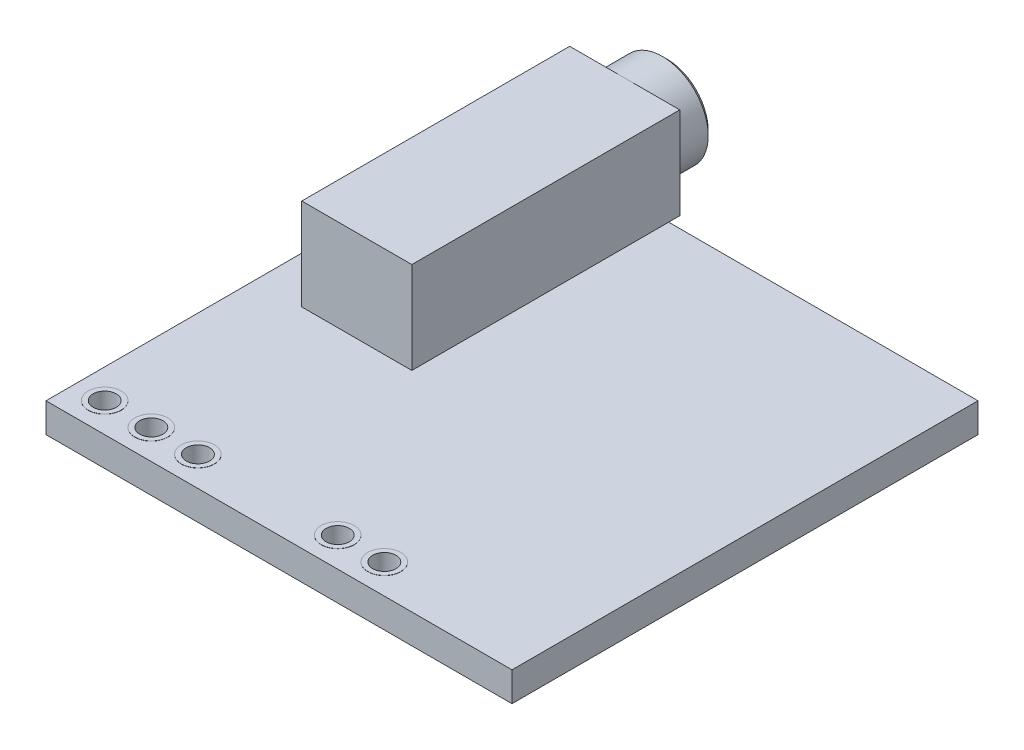
SolidWorks part; units mm, degrees
ref_plane "Front Plane" through (0, 0, 0) normal (0, 0, 1) x (1, 0, 0)
ref_plane "Top Plane" through (0, 0, 0) normal (0, 1, 0) x (1, 0, 0)
ref_plane "Right Plane" through (0, 0, 0) normal (1, 0, 0) x (0, 0, -1)
sketch "Sketch1" plane through (0, 0, 0) normal (0, 1, 0) x (1, 0, 0)
  line L0 (0, 0) -> (0, 12.7) construction
  line L1 (-12.7, 12.7) -> (12.7, 12.7)
  line L2 (-12.7, 12.7) -> (-12.7, -12.7)
  line L3 (-12.7, -12.7) -> (12.7, -12.7)
  line L4 (12.7, 12.7) -> (12.7, -12.7)
  line L5 (0, 0) -> (12.7, 0) construction
  dimension "D1" = 25.4
extrude "Boss-Extrude1" add sketch "Sketch1" along normal mid plane 1.6002
sketch "Sketch2" plane through (0, 0.8001, 0) normal (0, 1, 0) x (1, 0, 0)
  line L4 (-12.7, 12.7) -> (-12.7, -12.7)
  line L5 (-12.7, -12.7) -> (12.7, -12.7)
  line L6 (12.7, -12.7) -> (12.7, 12.7)
  line L7 (12.7, 12.7) -> (-12.7, 12.7)
  line L8 (-12.7, 12.7) -> (-12.7, -12.7)
  line L9 (-12.7, -12.7) -> (12.7, -12.7)
  line L10 (12.7, -12.7) -> (12.7, 12.7)
  line L11 (12.7, 12.7) -> (-12.7, 12.7)
  circle A0 centre (-11.0998, -11.0998) radius 0.635
  circle A1 centre (-8.5598, -11.0998) radius 0.635
  circle A2 centre (-6.0198, -11.0998) radius 0.635
  circle A3 centre (1.6002, -11.0998) radius 0.635
  circle A4 centre (4.1402, -11.0998) radius 0.635
  dimension "D8" = 1.27
  dimension "D2" = 1.6002
  dimension "D3" = 2.54
  dimension "D4" = 2.54
  dimension "D5" = 23.7998
  dimension "D6" = 7.62
  dimension "D7" = 2.54
  dimension "D1" = 0
extrude "Cut-Extrude1" cut sketch "Sketch2" against normal blind 1.6002 contours A0 | A1 | A2 | A3 | A4 region at (-11.0998, 0.8001, 11.0998) region at (-8.5598, 0.8001, 11.0998) region at (-6.0198, 0.8001, 11.0998) region at (1.6002, 0.8001, 11.0998) region at (4.1402, 0.8001, 11.0998)
sketch "Sketch3" plane through (0, 0.8001, 0) normal (0, 1, 0) x (1, 0, 0)
  line L0 (-7.16, 12.7) -> (-7.16, -1.3) construction
  line L2 (-10.16, 13.305) -> (-4.16, 13.305)
  line L3 (-10.16, 13.305) -> (-10.16, -1.3)
  line L4 (-12.7, 12.7) -> (-12.7, -12.7)
  line L5 (-12.7, -12.7) -> (12.7, -12.7)
  line L6 (12.7, -12.7) -> (12.7, 12.7)
  line L7 (12.7, 12.7) -> (-12.7, 12.7)
  line L8 (-12.7, 12.7) -> (-12.7, -12.7)
  line L9 (-12.7, -12.7) -> (12.7, -12.7)
  line L10 (12.7, -12.7) -> (12.7, 12.7)
  line L11 (12.7, 12.7) -> (-12.7, 12.7)
  line L12 (-10.16, -1.3) -> (-4.16, -1.3)
  line L13 (-4.16, 13.305) -> (-4.16, -1.3)
  line M13 (12.7, 12.7) -> (-12.7, 12.7)
  dimension "D2" = 6
  dimension "D3" = 2.54
  dimension "D4" = 14.605
  dimension "D5" = 14
  dimension "D1" = 0
extrude "Boss-Extrude2" add sketch "Sketch3" along normal blind 5 contours L0 L3 L12 M13 | L11 L0 L12 L13 | L13 L2 L3 L11 M13 region at (-5.66, 0.8001, -5.7) region at (-7.16, 0.8001, -13.0025) region at (-8.66, 0.8001, -5.7)
sketch "Sketch4" plane through (0, 0, -13.305) normal (0, 0, -1) x (-1, 0, 0)
  line L0 (7.16, 5.8001) -> (7.16, 0.8001) construction
  line L1 (4.16, 3.3001) -> (10.16, 3.3001) construction
  line L4 (4.16, 0.8001) -> (10.16, 0.8001)
  line L5 (10.16, 0.8001) -> (10.16, 5.8001)
  line L6 (10.16, 5.8001) -> (4.16, 5.8001)
  line L7 (4.16, 5.8001) -> (4.16, 0.8001)
  line L8 (4.16, 0.8001) -> (10.16, 0.8001)
  line L9 (10.16, 0.8001) -> (10.16, 5.8001)
  line L10 (10.16, 5.8001) -> (4.16, 5.8001)
  line L11 (4.16, 5.8001) -> (4.16, 0.8001)
  circle A0 centre (7.16, 3.3001) radius 2.5
  dimension "D2" = 5
  dimension "D1" = 0
extrude "Boss-Extrude3" add sketch "Sketch4" along normal blind 2.3 contours A0 region at (-7.16, 3.3001, -13.305)
sketch "Sketch5" plane through (0, 0, -15.605) normal (0, 0, -1) x (-1, 0, 0)
  circle A0 centre (7.16, 3.3001) radius 1.75
  circle A1 centre (7.16, 3.3001) radius 2.5
  circle A2 centre (7.16, 3.3001) radius 2.5
  dimension "D2" = 3.5
  dimension "D1" = 0
extrude "Cut-Extrude4" cut sketch "Sketch5" against normal offset from surface (15.905 mm away) 1 contours A0 region at (-7.16, 3.3001, -15.605) up to face at (-7.16, 3.3001, 1.3)
chamfer "Chamfer1" distance 0.25 angle 45 1 edges at (-9.66, 3.3001, -15.605)
sketch "Sketch6" plane through (0, 0.8001, 0) normal (0, 1, 0) x (1, 0, 0)
  line L8 (-10.16, -1.3) -> (-10.16, 12.7)
  line L9 (-10.16, 12.7) -> (-12.7, 12.7)
  line L10 (-12.7, 12.7) -> (-12.7, -12.7)
  line L11 (-12.7, -12.7) -> (12.7, -12.7)
  line L12 (12.7, -12.7) -> (12.7, 12.7)
  line L13 (12.7, 12.7) -> (-4.16, 12.7)
  line L14 (-4.16, 12.7) -> (-4.16, -1.3)
  line L15 (-4.16, -1.3) -> (-10.16, -1.3)
  line L16 (-10.16, -1.3) -> (-10.16, 12.7)
  line L17 (-10.16, 12.7) -> (-12.7, 12.7)
  line L18 (-12.7, 12.7) -> (-12.7, -12.7)
  line L19 (-12.7, -12.7) -> (12.7, -12.7)
  line L20 (12.7, -12.7) -> (12.7, 12.7)
  line L21 (12.7, 12.7) -> (-4.16, 12.7)
  line L22 (-4.16, 12.7) -> (-4.16, -1.3)
  line L23 (-4.16, -1.3) -> (-10.16, -1.3)
  circle A0 centre (-11.0998, -11.0998) radius 0.635 construction
  circle A1 centre (-8.5598, -11.0998) radius 0.635 construction
  circle A2 centre (-6.0198, -11.0998) radius 0.635 construction
  circle A3 centre (1.6002, -11.0998) radius 0.635 construction
  circle A4 centre (4.1402, -11.0998) radius 0.635 construction
  circle A5 centre (-11.0998, -11.0998) radius 0.635
  circle A6 centre (-8.5598, -11.0998) radius 0.635
  circle A7 centre (-6.0198, -11.0998) radius 0.635
  circle A8 centre (1.6002, -11.0998) radius 0.635
  circle A9 centre (4.1402, -11.0998) radius 0.635
  circle A10 centre (-11.0998, -11.0998) radius 0.9
  circle A11 centre (-8.5598, -11.0998) radius 0.9
  circle A12 centre (-6.0198, -11.0998) radius 0.9
  circle A13 centre (1.6002, -11.0998) radius 0.9
  circle A14 centre (4.1402, -11.0998) radius 0.9
  circle M17 centre (4.1402, -11.0998) radius 0.635
  circle M18 centre (1.6002, -11.0998) radius 0.635
  circle M19 centre (-6.0198, -11.0998) radius 0.635
  circle M20 centre (-8.5598, -11.0998) radius 0.635
  circle M21 centre (-11.0998, -11.0998) radius 0.635
  dimension "D2" = 1.8
  dimension "D1" = 0
extrude "Boss-Extrude4" add sketch "Sketch6" along normal blind 0.01 contours A10 M21 | A11 M20 | A12 M19 | A13 M18 | A14 M17 region at (-11.9743, 0.8001, 11.0998) region at (-9.4343, 0.8001, 11.0998) region at (-6.8943, 0.8001, 11.0998) region at (0.7257, 0.8001, 11.0998) region at (3.2657, 0.8001, 11.0998)
mirror "Mirror1" about plane through (0, 0, 0) normal (0, 1, 0) of "Boss-Extrude4"
ref_axis "Axis1" through (-7.16, 3.3001, 0.3) along (0, 0, -1)
